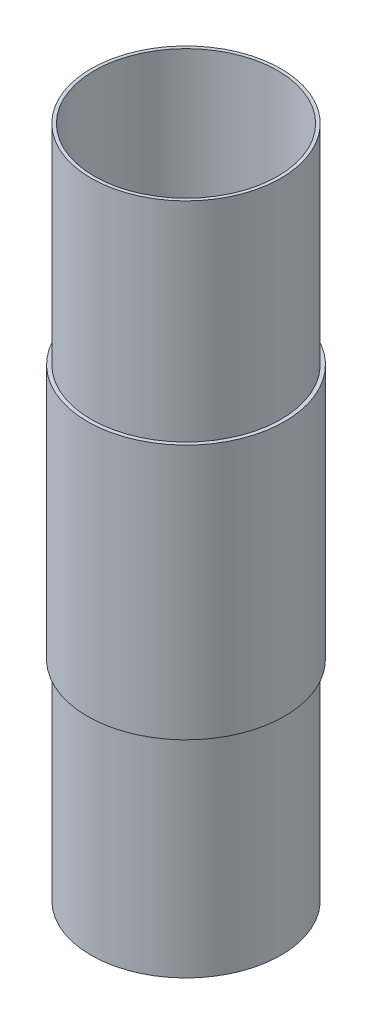
SolidWorks part; units mm, degrees
ref_plane "Front Plane" through (0, 0, 0) normal (0, 0, 1) x (1, 0, 0)
ref_plane "Top Plane" through (0, 0, 0) normal (0, 1, 0) x (1, 0, 0)
ref_plane "Right Plane" through (0, 0, 0) normal (1, 0, 0) x (0, 0, -1)
sketch "Sketch1" plane through (0, 0, 0) normal (0, 1, 0) x (1, 0, 0)
  circle A0 centre (0, 0) radius 42.5
  circle A1 centre (0, 0) radius 40.9
  circle A2 centre (0, 0) radius 39.5
  dimension "D1" = 85
  dimension "D2" = 81.8
  dimension "D3" = 79
extrude "Boss-Extrude1" add sketch "Sketch1" along normal mid plane 290 contours A1 A2 region at (-39.7432, 0, 0)
extrude "Boss-Extrude2" add sketch "Sketch1<3>" along normal mid plane 110 contours A0 A1 region at (-41.2979, 0, 0)
sketch "Sketch1<3>" plane through (0, 0, 0) normal (0, 1, 0) x (1, 0, 0) same geometry as "Sketch1"
